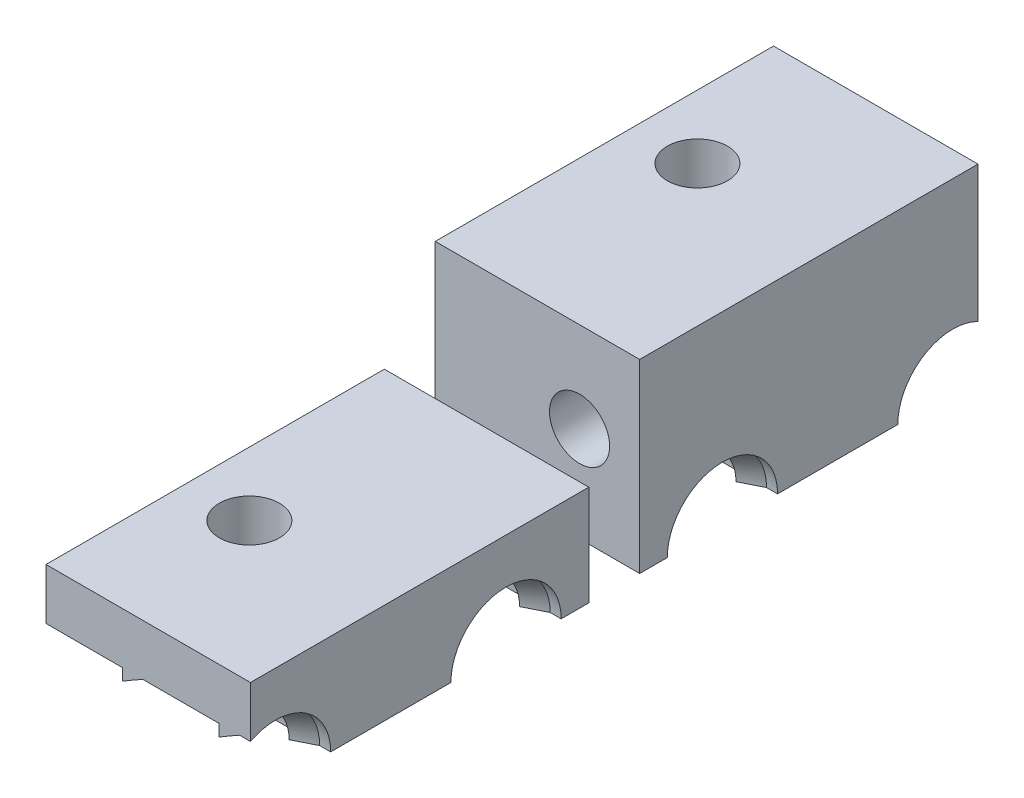
SolidWorks part; units mm, degrees
ref_plane "Front Plane" through (0, 0, 0) normal (0, 0, 1) x (1, 0, 0)
ref_plane "Top Plane" through (0, 0, 0) normal (0, 1, 0) x (1, 0, 0)
ref_plane "Right Plane" through (0, 0, 0) normal (1, 0, 0) x (0, 0, -1)
sketch "Sketch6" plane through (0, 0, 0) normal (0, 1, 0) x (1, 0, 0)
  line L0 (0, 0) -> (0, 5)
  line L1 (0, 5) -> (12.7, 5)
  line L2 (12.7, 5) -> (12.7, 2.75)
  line L6 (12.7, 2.75) -> (9.652, 2.75)
  line L7 (9.652, 2.75) -> (8.636, 2.242)
  line L8 (8.636, 2.242) -> (8.636, 2.75)
  line L9 (8.636, 2.75) -> (4.826, 2.75)
  line L10 (4.826, 2.75) -> (3.81, 2.242)
  line L11 (3.81, 2.242) -> (3.81, 2.75)
  line L12 (3.81, 2.75) -> (0, 2.75)
  line L18 (0, 0) -> (15, 0)
  dimension "D1" = 0.508
  dimension "D2" = 12.7
  dimension "D3" = 3.048
  dimension "D4" = 5
  dimension "D5" = 2.25
  dimension "D6" = 2.25
  dimension "D7" = 2.25
  dimension "D10" = 1.016
  dimension "D11" = 1.016
  dimension "D12" = 3.81
  dimension "D13" = 3.81
  dimension "D20" = 15
revolve "Revolve1" add sketch "Sketch6" angle 180 about L18 region at (6.3538, 0, -3.852)
sketch "Sketch9" plane through (0, 0, 0) normal (0, 0, 1) x (1, 0, 0)
  line L0 (0, 0) -> (0, 3.25)
  line L1 (0, 3.25) -> (0, 5)
  line L2 (0, 5) -> (12.7, 5)
  line L3 (12.7, 5) -> (12.7, 2.75)
  line L4 (12.7, 2.75) -> (12.7, 0)
  line L5 (12.7, 0) -> (0, 0)
  line L6 (0, 3.25) -> (12.7, 2.75)
  dimension "D1" = 3.25
extrude "Boss-Extrude1" add sketch "Sketch9" along normal blind 9.25 and the other way blind 9.25 contours L1 L6 L3 L2 region at (6.6146, 3.9948, 0)
extrude "Boss-Extrude2" add sketch "Sketch9<3>" along normal blind 5.75 from offset 3.5 contours L6 L0 L5 L4 region at (6.1736, 1.5035, 0)
sketch "Sketch9<3>" plane through (0, 0, 0) normal (0, 0, 1) x (1, 0, 0) same geometry as "Sketch9"
extrude "Boss-Extrude3" add sketch "Sketch9<4>" against normal blind 5.75 from offset 3.5 contours L6 L0 L5 L4 region at (6.1736, 1.5035, 0) offset against normal yes
sketch "Sketch9<4>" plane through (0, 0, 0) normal (0, 0, 1) x (1, 0, 0) same geometry as "Sketch9"
sketch "Sketch14" plane through (0, 0, 0) normal (-1, 0, 0) x (0, 0, 1)
  line L0 (-9.25, 5) -> (9.25, 5) construction
  line L1 (-9.25, 0) -> (-6.75, 0)
  line L2 (-9.25, 0) -> (-9.25, 5)
  line L3 (-9.25, 5) -> (-6.75, 5)
  line L4 (-6.75, 0) -> (-6.75, 5)
  dimension "D1" = 2.5
extrude "Cut-Extrude10" cut sketch "Sketch14" against normal through all
ref_plane "Plane3" through (0, 0, -5.75) normal (0, 0, 1) x (1, 0, 0)
mirror "Mirror4" about plane through (0, 0, -5.75) normal (0, 0, 1) of bodies 150 146
sketch "Sketch13" plane through (0, 0, 0) normal (-1, 0, 0) x (0, 0, 1)
  line L0 (-2.75, 0) -> (-8.75, 0) construction
  line L1 (-2.75, 0) -> (2.75, 0)
  line L2 (-2.75, 0) -> (-2.75, 2.75)
  line L3 (-2.75, 2.75) -> (2.75, 2.75)
  line L4 (2.75, 0) -> (2.75, 2.75)
  point P6 (0, 0)
  dimension "D1" = 5.5
  dimension "D2" = 2.75
extrude "Cut-Extrude9" cut sketch "Sketch13" against normal blind 1.75
sketch "Sketch15" plane through (0, 5, 0) normal (0, 1, 0) x (1, 0, 0)
  line L0 (0, 20.75) -> (0, -9.25) construction
  line L1 (12.7, 20.75) -> (0, 20.75)
  line L2 (12.7, 20.75) -> (12.7, 12.75)
  line L3 (12.7, 12.75) -> (0, 12.75)
  line L4 (0, 20.75) -> (0, 12.75)
  dimension "D1" = 8
extrude "Cut-Extrude11" cut sketch "Sketch15" against normal through all
sketch "Sketch16" plane through (0, 0, 0) normal (-1, 0, 0) x (0, 0, 1)
  line L0 (-12.75, 5) -> (9.25, 5) construction
  line L1 (9.25, 0) -> (4.1274, 0)
  line L2 (9.25, 0) -> (9.25, 5)
  line L3 (9.25, 5) -> (4.1274, 5)
  line L4 (4.1274, 0) -> (4.1274, 5)
extrude "Cut-Extrude12" cut sketch "Sketch16" against normal through all
sketch "Sketch22" plane through (0, 0, 4.1274) normal (0, 0, 1) x (1, 0, 0)
  line L0 (12.7, 0) -> (0, 0) construction
  line L1 (12.7, 5) -> (10.2, 5)
  line L2 (12.7, 5) -> (12.7, 0)
  line L3 (12.7, 0) -> (10.2, 0)
  line L4 (10.2, 5) -> (10.2, 0)
  dimension "D1" = 2.5
extrude "Cut-Extrude17" cut sketch "Sketch22" against normal through all
ref_plane "Plane5" through (0, 0, 5.3974) normal (0, 0, 1) x (1, 0, 0)
mirror "Mirror8" about plane through (0, 0, 5.3974) normal (0, 0, 1) of bodies 160 152
sketch "Sketch17" plane through (0, 5, 0) normal (0, 1, 0) x (1, 0, 0)
  line L1 (0, -4.1274) -> (10.2, -4.1274)
  line L2 (0, -4.1274) -> (0, 12.75)
  line L3 (0, 12.75) -> (10.2, 12.75)
  line L4 (10.2, -4.1274) -> (10.2, 12.75)
extrude "Boss-Extrude4" add sketch "Sketch17" along normal blind 4.25
sketch "Sketch18" plane through (0, 9.25, 0) normal (0, 1, 0) x (1, 0, 0)
  line L0 (10.2, -4.1274) -> (10.2, 12.75) construction
  line L1 (0, 12.75) -> (0, -4.1274) construction
  line L2 (0, -4.1274) -> (10.2, -4.1274) construction
  circle A0 centre (3.175, 5.7786) radius 1.5
  circle A1 centre (7.025, 5.7786) radius 1.5
  dimension "D1" = 3
  dimension "D2" = 3
  dimension "D3" = 3.175
  dimension "D4" = 3.175
  dimension "D5" = 9.906
extrude "Cut-Extrude13" cut sketch "Sketch18" against normal through all contours A0 region at (3.175, 9.25, -5.7786)
sketch "Sketch19" plane through (0, 5, 0) normal (0, 1, 0) x (1, 0, 0)
  line L0 (0, -23.5447) -> (0, -6.6674) construction
  line L2 (10.2, -6.6674) -> (0, -6.6674) construction
  circle A0 centre (3.175, -16.5734) radius 1.5
  dimension "D4" = 3
  dimension "D1" = 3.175
  dimension "D5" = 9.906
extrude "Cut-Extrude14" cut sketch "Sketch19" against normal through all
sketch "Sketch20" plane through (0, 0, 4.1274) normal (0, 0, 1) x (1, 0, 0)
  line L0 (10.2, 9.25) -> (10.2, 0) construction
  line L1 (0, 9.25) -> (10.2, 9.25) construction
  circle A0 centre (7.2, 4.75) radius 1.5
  dimension "D1" = 3
  dimension "D2" = 3
  dimension "D3" = 4.5
extrude "Cut-Extrude16" cut sketch "Sketch20" against normal through all
